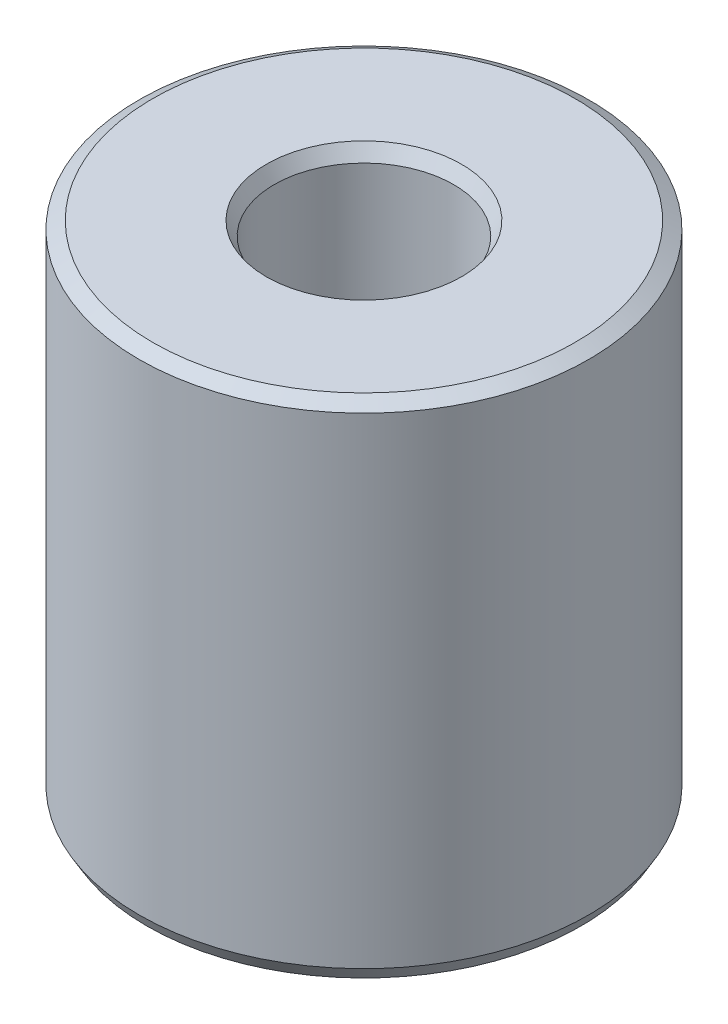
SolidWorks part; units mm, degrees
ref_plane "Front Plane" through (0, 0, 0) normal (0, 0, 1) x (1, 0, 0)
ref_plane "Top Plane" through (0, 0, 0) normal (0, 1, 0) x (1, 0, 0)
ref_plane "Right Plane" through (0, 0, 0) normal (1, 0, 0) x (0, 0, -1)
sketch "Sketch1" plane through (0, 0, 0) normal (0, 1, 0) x (1, 0, 0)
  circle A0 centre (0, 0) radius 57.5
  dimension "SLEEVE_OD" = 115
extrude "Boss-Extrude1" add sketch "Sketch1" along normal blind 128.5165
sketch "Sketch2" plane through (0, 0, 0) normal (0, 1, 0) x (1, 0, 0)
  circle A0 centre (0, 0) radius 22.9335
  dimension "BORE_D" = 45.867
extrude "Cut-Extrude1" cut sketch "Sketch2" along normal through all
chamfer "Chamfer1" distance 2.0163 angle 60 4 edges at (0, 128.5165, 22.9335) (0, 0, 22.9335) (0, 0, 57.5) (0, 128.5165, 57.5) first distance on face at (0, 128.5165, 22.9335) first distance on face at (0, 0, 22.9335) first distance on face at (0, 128.5165, 57.5)
